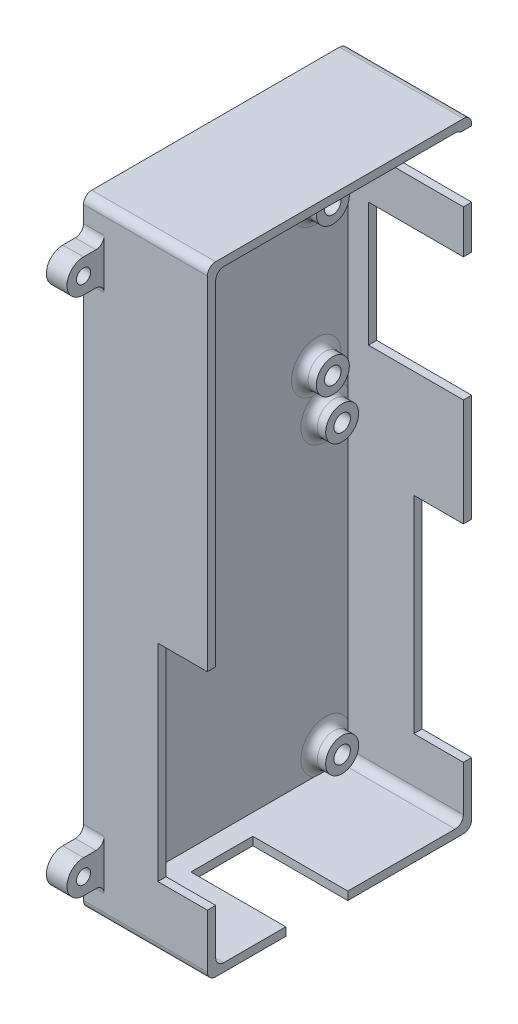
SolidWorks part; units mm, degrees
ref_plane "Front Plane" through (0, 0, 0) normal (1, 0, 0) x (0, 1, 0)
ref_plane "Top Plane" through (0, 0, 0) normal (0, 0, 1) x (0, 1, 0)
ref_plane "Right Plane" through (0, 0, 0) normal (0, 1, 0) x (-1, 0, 0)
sketch "Sketch1" plane through (0, 0, 0) normal (1, 0, 0) x (0, 1, 0)
  line L1 (75, -32) -> (-75, -32)
  line L2 (75, -32) -> (75, 32)
  line L3 (75, 32) -> (-75, 32)
  line L4 (-75, -32) -> (-75, 32)
  line L5 (75, -32) -> (-75, 32) construction
  line L6 (75, 32) -> (-75, -32) construction
  point P0 (0, 0)
  point P5 (0, 0)
  dimension "D1" = 150
  dimension "D2" = 64
extrude "Boss-Extrude1" add sketch "Sketch1" along normal blind 30
shell "Shell1" thickness 2
sketch "Sketch2" plane through (2, 0, 0) normal (1, 0, 0) x (0, 1, 0)
  circle A0 centre (-67.698, 24.892) radius 4
  circle A1 centre (1.898, 24.892) radius 4
  circle A2 centre (1.898, -24.638) radius 4
  circle A3 centre (-67.698, -24.638) radius 4
  circle A4 centre (12.915, 22.375) radius 4
  circle A5 centre (48.665, 22.375) radius 4
  circle A6 centre (12.915, -22.375) radius 4
  circle A7 centre (48.665, -22.375) radius 4
  circle A8 centre (64.18, -9.4) radius 5
  dimension "D1" = 8
  dimension "D2" = 10
extrude "Mount boss" add sketch "Sketch2" along normal blind 4
sketch "Sketch3" plane through (6, 0, 0) normal (1, 0, 0) x (0, 1, 0)
  circle A0 centre (-67.698, 24.892) radius 2
  circle A1 centre (1.898, 24.892) radius 2
  circle A2 centre (1.898, -24.638) radius 2
  circle A3 centre (-67.698, -24.638) radius 2
  circle A4 centre (12.915, 22.375) radius 2
  circle A5 centre (48.665, 22.375) radius 2
  circle A6 centre (48.665, -22.375) radius 2
  circle A7 centre (12.915, -22.375) radius 2
  circle A8 centre (64.18, -9.4) radius 2.5
  dimension "D1" = 4
  dimension "D2" = 5
extrude "M2.5 insert recess" cut sketch "Sketch3" against normal blind 4
fillet "Fillet1" radius 2 9 edges at (2, -67.698, -28.638) (2, 1.898, -28.638) (2, 12.915, -26.375) (2, 48.665, -26.375) (2, 64.18, -14.4) (2, 48.665, 18.375) (2, 12.915, 18.375) (2, 1.898, 20.892) (2, -67.698, 20.892)
sketch "Sketch4" plane through (30, 0, 0) normal (1, 0, 0) x (0, 1, 0)
  line L0 (-73, 30) -> (-73, -30) construction
  line L1 (-75, 13) -> (-73, 13)
  line L2 (-75, 13) -> (-75, -2)
  line L3 (-75, -2) -> (-73, -2)
  line L4 (-75, 32) -> (-75, -32)
  line L5 (-75, -32) -> (75, -32)
  line L6 (75, -32) -> (75, 32)
  line L7 (75, 32) -> (-75, 32)
  line L8 (-75, 32) -> (-75, -32)
  line L9 (-75, -32) -> (75, -32)
  line L10 (75, -32) -> (75, 32)
  line L11 (75, 32) -> (-75, 32)
  line L12 (-73, 13) -> (-73, -2)
  line L13 (-73, -30) -> (73, -30) construction
  line L14 (16, -30) -> (46, -30)
  line L15 (16, -30) -> (16, -32)
  line L16 (16, -32) -> (46, -32)
  line L17 (46, -30) -> (46, -32)
  line L19 (56.5, -30) -> (72.5, -30)
  line L20 (56.5, -30) -> (56.5, -32)
  line L21 (56.5, -32) -> (72.5, -32)
  line L22 (72.5, -30) -> (72.5, -32)
  line M16 (-73, -30) -> (-73, 30)
  line M19 (73, -30) -> (-73, -30)
  line M20 (-75, 32) -> (-75, -32)
  dimension "D2" = 15
  dimension "D3" = 19
  dimension "D4" = 30
  dimension "D5" = 29
  dimension "D6" = 16
  dimension "D7" = 2.5
  dimension "D1" = 0
extrude "Cut-Extrude2" cut sketch "Sketch4" against normal blind 23 contours L3 L1 M20 M16 | L17 L15 L9 M19 | L22 L20 L9 M19
sketch "Sketch5" plane through (30, 0, 0) normal (1, 0, 0) x (0, 1, 0)
  line L0 (75, 32) -> (-75, 32) construction
  line L1 (-60, 32) -> (-10, 32)
  line L2 (-60, 32) -> (-60, 30)
  line L3 (-60, 30) -> (-10, 30)
  line L4 (-10, 32) -> (-10, 30)
  line L5 (73, 30) -> (-73, 30) construction
  line L6 (-75, 32) -> (-75, 13) construction
  dimension "D1" = 50
  dimension "D2" = 15
extrude "Cut-Extrude3" cut sketch "Sketch5" against normal blind 12
mirror "Mirror1" about plane through (0, 0, 0) normal (0, 0, 1) of "Cut-Extrude3"
fillet "Fillet2" radius 2 8 edges at (15, 75, 32) (15, -75, 32) (15, -75, -32) (15, 75, -32) (16, 73, -30) (16, -73, -30) (16, 73, 30) (16, -73, 30)
sketch "Sketch6" plane through (0, 0, 0) normal (-1, 0, 0) x (0, -1, 0)
  line L0 (67, 32) -> (67, 37)
  line L1 (-73, 32) -> (73, 32) construction
  line L2 (59, 37) -> (59, 32)
  line L3 (75, 30) -> (75, -30) construction
  line L8 (73, 32) -> (-73, 32)
  line L9 (-75, 30) -> (-75, -30)
  line L10 (-73, -32) -> (73, -32)
  line L11 (75, -30) -> (75, 30)
  line L12 (73, 32) -> (-73, 32)
  line L13 (-75, 30) -> (-75, -30)
  line L14 (-73, -32) -> (73, -32)
  line L15 (75, -30) -> (75, 30)
  arc A0 (67, 37) -> (59, 37) centre (63, 37) ccw
  arc A5 (-73, 32) -> (-75, 30) centre (-73, 30) ccw
  arc A6 (-75, -30) -> (-73, -32) centre (-73, -30) ccw
  arc A7 (73, -32) -> (75, -30) centre (73, -30) ccw
  arc A8 (75, 30) -> (73, 32) centre (73, 30) ccw
  arc A9 (-73, 32) -> (-75, 30) centre (-73, 30) ccw
  arc A10 (-75, -30) -> (-73, -32) centre (-73, -30) ccw
  arc A11 (73, -32) -> (75, -30) centre (73, -30) ccw
  arc A12 (75, 30) -> (73, 32) centre (73, 30) ccw
  line M3 (73, 32) -> (-73, 32)
  dimension "D1" = 4
  dimension "D2" = 8
  dimension "D3" = 5
  dimension "D4" = 0
extrude "Mount tab" add sketch "Sketch6" against normal blind 5 contours L0 A0 L2 M3
hole_wizard "M3 Clearance Hole1" positions "Sketch7" profile "Sketch8" hole size "M3" standard "ANSI Metric" end condition through all
sketch "Sketch7" plane through (5, 0, 0) normal (1, 0, 0) x (0, 1, 0)
  point P0 (-63, 37)
sketch "Sketch8" plane through (5, -63, 37) normal (0, 1, 0) x (0, 0, -1)
  line L0 (0, 0) -> (0, 5)
  line L1 (0, 5) -> (1.7, 5)
  line L2 (1.7, 5) -> (1.7, 0)
  line L5 (1.7, 0) -> (0, 0)
  line L11 (0, -6.35) -> (0, 107.95) construction
  dimension "Thru Hole Dia." = 3.4
  dimension "Thru Hole Depth" = 5
mirror "Mirror2" about plane through (0, 0, 0) normal (0, 1, 0) of "M3 Clearance Hole1", "Mount tab" second plane through (0, 0, 0) second plane normal (0, 0, 1)
fillet "Fillet3" radius 2 8 edges at (2.5, -67, 32) (2.5, -59, 32) (2.5, -67, -32) (2.5, -59, -32) (2.5, 67, 32) (2.5, 59, 32) (2.5, 67, -32) (2.5, 59, -32)
